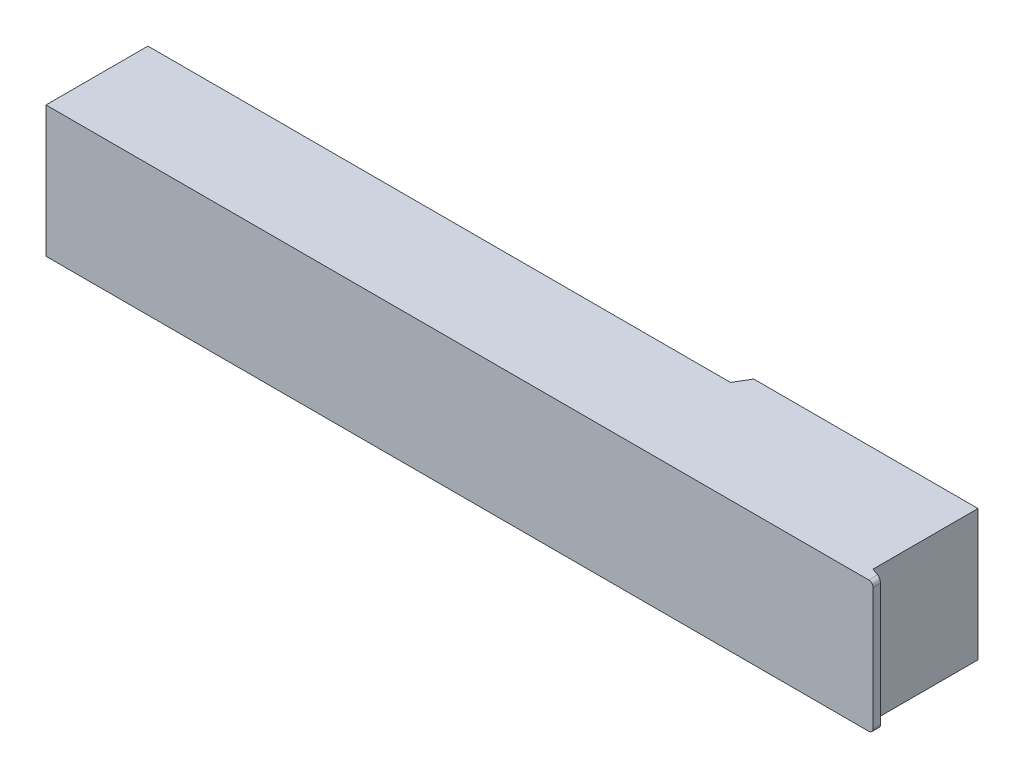
SolidWorks part; units mm, degrees
ref_plane "Front Plane" through (0, 0, 0) normal (1, 0, 0) x (0, 1, 0)
ref_plane "Top Plane" through (0, 0, 0) normal (0, 0, 1) x (0, 1, 0)
ref_plane "Right Plane" through (0, 0, 0) normal (0, 1, 0) x (-1, 0, 0)
sketch "Sketch1" plane through (0, 0, 0) normal (0, 0, 1) x (0, 1, 0)
  line L1 (0, 0) -> (22.5, 0)
  line L2 (0, 0) -> (0, -142)
  line L3 (0, -142) -> (22.5, -142)
  line L4 (22.5, 0) -> (22.5, -142)
extrude "Boss-Extrude1" add sketch "Sketch1" against normal blind 20 contours L2 L3 L4 L1
sketch "Sketch2" plane through (142, 0, 0) normal (1, 0, 0) x (0, 1, 0)
  line L0 (22.5, -20) -> (22.5, 0) construction
  line L1 (0, -20) -> (22.5, -20)
  line L2 (0, -20) -> (0, -2)
  line L3 (0, -2) -> (22.5, -2)
  line L4 (22.5, -20) -> (22.5, -2)
  point P7 (0, 0)
  point P8 (0, 0)
extrude "Cut-Extrude1" cut sketch "Sketch2" against normal blind 2 contours L3 L4 L1 L2
chamfer "Chamfer5" distance 0.75 angle 70 1 edges at (142, 11.25, -2) first distance on face at (142, 11.25, -1)
fillet "Fillet5" radius 0.75 2 edges at (142, 0, -0.625) (142, 22.5, -0.625)
sketch "Sketch3" plane through (0, 22.5, 0) normal (0, 1, 0) x (-1, 0, 0)
  line L0 (0, 0) -> (-141.25, 0) construction
  line L1 (-140, -20) -> (-30, -20)
  line L2 (-140, -20) -> (-140, 0)
  line L3 (-140, 0) -> (-30, 0)
  line L4 (-30, -20) -> (-30, 0)
  line L5 (0, -20) -> (0, 0) construction
  line L6 (-30, -20) -> (0, -20)
  line L7 (-30, -20) -> (-30, -10)
  line L8 (-30, -10) -> (0, -10)
  line L9 (0, -20) -> (0, -10)
  line L11 (-30, 0) -> (0, 0)
  line L12 (-30, 0) -> (-30, -2.5)
  line L17 (-30, -2.5) -> (0, -2.5)
  line L18 (0, 0) -> (0, -2.5)
extrude "Cut-Extrude2" [suppressed] cut sketch "Sketch3" against normal up to surface (22.5 mm away) contours L12 L17 L18 L11 up to face at (93.75, 0, -7.2502)
sketch3d "3DSketch1" plane through (0, 0, 0) normal (0, 0, 1) x (1, 0, 0)
  dimension "D1" = 11.25
sketch "Sketch4" plane through (0, 11.25, 0) normal (0, 1, 0) x (1, 0, 0)
  line L0 (30, 20) -> (165, 20)
  line L1 (140, 20) -> (30, 20) construction
  line L2 (165, 20) -> (165, 7.5)
  line L3 (165, 7.5) -> (30, 20)
  dimension "D1" = 12.5
  dimension "D2" = 135
sketch "Sketch5" plane through (0, 0, -20) normal (0, 0, -1) x (-1, 0, 0)
  line L0 (0, 22.5) -> (-140, 22.5) construction
  line L1 (-140, 0) -> (-91.5, 0)
  line L2 (-140, 0) -> (-140, 22.5)
  line L3 (-140, 22.5) -> (-91.5, 22.5)
  line L4 (-91.5, 0) -> (-91.5, 22.5)
  line L5 (-138, 2) -> (-93.5, 2)
  line L6 (-93.5, 2) -> (-93.5, 20.5)
  line L7 (-138, 20.5) -> (-93.5, 20.5)
  line L8 (-138, 2) -> (-138, 20.5)
  line L9 (-93.5, 20.5) -> (-91.5, 22.5)
  line L10 (-93.5, 2) -> (-91.5, 0)
  line L12 (-91.5, 22.5) -> (0, 22.5)
  line L13 (-91.5, 22.5) -> (-91.5, 0)
  line L14 (-91.5, 0) -> (0, 0)
  line L15 (0, 22.5) -> (0, 0)
  line M6 (-140, 0) -> (0, 0)
  line M7 (0, 0) -> (0, 22.5)
  line M8 (0, 22.5) -> (-140, 22.5)
  dimension "D1" = 2
extrude "Cut-Extrude3" [suppressed] cut sketch "Sketch5" against normal blind 7.5 contours L8 L5 L6 L7 | L6 L10 L4 L9 | L4 M6 M7 M8
sketch "Sketch6" plane through (0, 22.5, 0) normal (0, 1, 0) x (-1, 0, 0)
  line L0 (-100, -17.5) -> (-101.5, -20)
  line L1 (-140, -20) -> (-100, -20) construction
  line L2 (-140, -20) -> (-140, -17.5) construction
  line L3 (-140, -17.5) -> (-100, -17.5) construction
  line L4 (-100, -20) -> (-100, -17.5) construction
  line L6 (-100, -20) -> (-101.5, -20)
  line L7 (-100, -17.5) -> (0, -17.5)
  line L8 (-100, -17.5) -> (-100, -20) construction
  line L9 (-100, -20) -> (0, -20)
  line L10 (0, -17.5) -> (0, -20)
  dimension "D1" = 100
  dimension "D2" = 101.5
extrude "Cut-Extrude4" cut sketch "Sketch6" against normal through all and the other way through all
equation "\"whitekey_cutout_length\"= 101.5"
equation "\"mount_recess_length\"=50"
equation "\"mount_recess_height\"=12.5"
equation "\"mount_recess_depth\"=1.5"
equation "\"D1@Sketch6\"=\"whitekey_cutout_length\"-1.5"
equation "\"D2@Sketch6\"=\"whitekey_cutout_length\""
